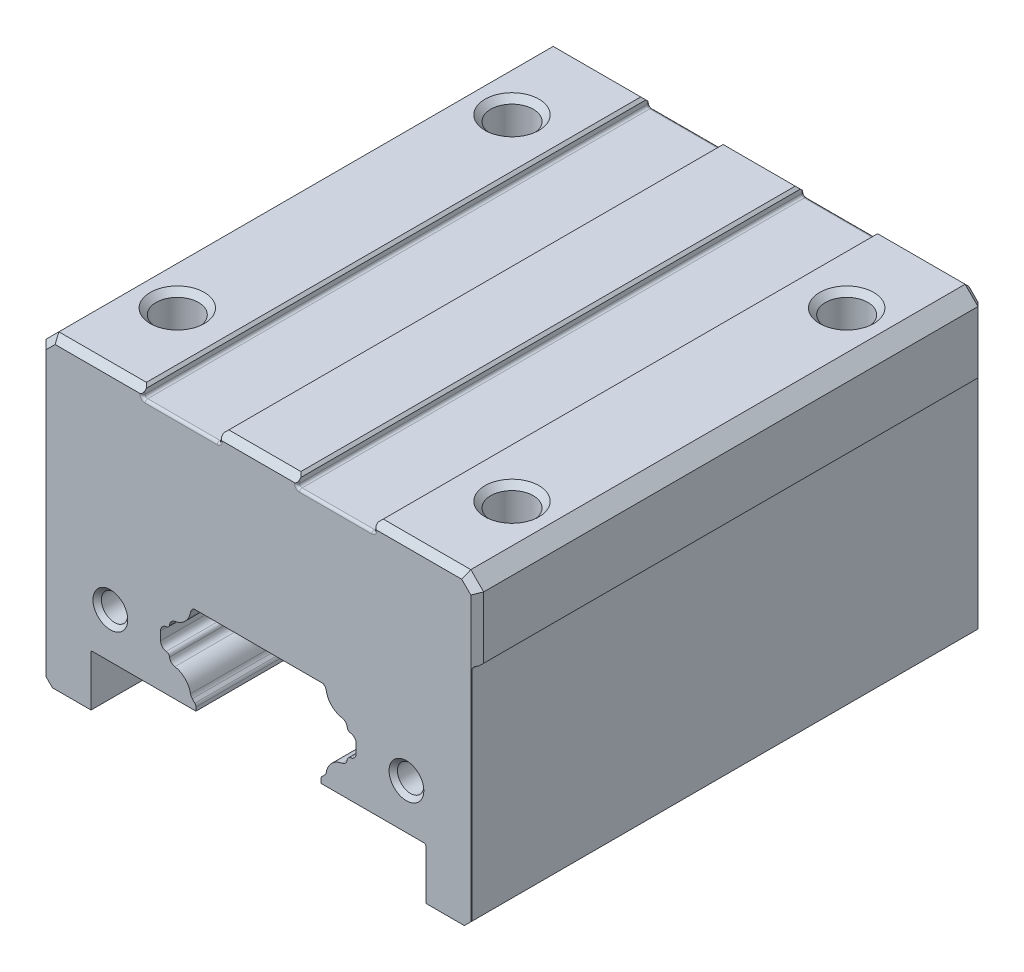
SolidWorks part; units mm, degrees
material "Plain Carbon Steel"
ref_plane "Front Plane" through (0, 0, 0) normal (0, 0, 1) x (1, 0, 0)
ref_plane "Top Plane" through (0, 0, 0) normal (0, 1, 0) x (1, 0, 0)
ref_plane "Right Plane" through (0, 0, 0) normal (1, 0, 0) x (0, 0, -1)
sketch "Rail Profile" plane through (0, 0, 0) normal (0, 0, 1) x (1, 0, 0)
  line L47 (0, 0) -> (0, 28) construction
  line L48 (-7, 0) -> (7, 0)
  line L49 (7, 0) -> (7.5, 0.5)
  line L50 (7.5, 0.5) -> (7.5, 3.0858)
  line L58 (7.2071, 3.7929) -> (4.8672, 6.1328)
  line L59 (4.75, 6.4157) -> (4.75, 8.5843)
  line L60 (4.8672, 8.8672) -> (5.063, 9.063)
  line L61 (7.5, 11.6657) -> (7.5, 12.3343)
  line L62 (-7, 0) -> (-7.5, 0.5)
  line L63 (5, 15) -> (-5, 15)
  line L64 (6.75, 9) -> (6.75, 15) construction
  line L65 (5.063, 14.937) -> (5, 15)
  line L66 (-7.5, 0.5) -> (-7.5, 3.0858)
  line L67 (6.75, 15) -> (3.75, 12) construction
  line L68 (3.75, 12) -> (6.75, 9) construction
  line L69 (7.1, 12.3343) -> (7.1, 11.6657) construction
  line L70 (6.4042, 13.0301) -> (6.4042, 10.9699) construction
  line L71 (-7.2071, 3.7929) -> (-4.8672, 6.1328)
  line L72 (-4.75, 6.4157) -> (-4.75, 8.5843)
  line L73 (-4.8672, 8.8672) -> (-5.063, 9.063)
  line L74 (5, 15) -> (8, 12) construction
  line L75 (4.8672, 8.8672) -> (8, 12) construction
  line L76 (-7.5, 11.6657) -> (-7.5, 12.3343)
  line L77 (-5.063, 14.937) -> (-5, 15)
  arc A4 (6.4734, 13.4241) -> (5.1741, 14.7234) centre (6.75, 15) cw
  arc A6 (5.1741, 9.2766) -> (6.4734, 10.5759) centre (6.75, 9) cw
  arc A7 (7.2071, 3.7929) -> (7.5, 3.0858) centre (6.5, 3.0858) cw
  arc A8 (5.063, 14.937) -> (5.1741, 14.7234) centre (4.7801, 14.6542) cw
  arc A9 (6.4734, 13.4241) -> (6.8012, 13.0792) centre (6.4042, 13.0301) cw
  arc A10 (7.1491, 12.7313) -> (7.5, 12.3343) centre (7.1, 12.3343) cw
  arc A11 (7.5, 11.6657) -> (7.1491, 11.2687) centre (7.1, 11.6657) cw
  arc A12 (6.8012, 10.9208) -> (6.4734, 10.5759) centre (6.4042, 10.9699) cw
  arc A13 (5.1741, 9.2766) -> (5.063, 9.063) centre (4.7801, 9.3458) cw
  arc A14 (4.8672, 8.8672) -> (4.75, 8.5843) centre (5.15, 8.5843) ccw
  arc A15 (4.75, 6.4157) -> (4.8672, 6.1328) centre (5.15, 6.4157) ccw
  arc A16 (6.8012, 13.0792) -> (7.1491, 12.7313) centre (7.1981, 13.1283) ccw
  arc A17 (7.1491, 11.2687) -> (6.8012, 10.9208) centre (7.1981, 10.8717) ccw
  arc A18 (-7.2071, 3.7929) -> (-7.5, 3.0858) centre (-6.5, 3.0858) ccw
  arc A19 (-4.75, 6.4157) -> (-4.8672, 6.1328) centre (-5.15, 6.4157) cw
  arc A20 (-4.8672, 8.8672) -> (-4.75, 8.5843) centre (-5.15, 8.5843) cw
  arc A21 (-5.1741, 9.2766) -> (-5.063, 9.063) centre (-4.7801, 9.3458) ccw
  arc A22 (-5.1741, 9.2766) -> (-6.4734, 10.5759) centre (-6.75, 9) ccw
  arc A23 (-6.8012, 10.9208) -> (-6.4734, 10.5759) centre (-6.4042, 10.9699) ccw
  arc A24 (-7.1491, 11.2687) -> (-6.8012, 10.9208) centre (-7.1981, 10.8717) cw
  arc A25 (-7.5, 11.6657) -> (-7.1491, 11.2687) centre (-7.1, 11.6657) ccw
  arc A26 (-7.1491, 12.7313) -> (-7.5, 12.3343) centre (-7.1, 12.3343) ccw
  arc A27 (-6.8012, 13.0792) -> (-7.1491, 12.7313) centre (-7.1981, 13.1283) cw
  arc A28 (-6.4734, 13.4241) -> (-6.8012, 13.0792) centre (-6.4042, 13.0301) ccw
  arc A29 (-6.4734, 13.4241) -> (-5.1741, 14.7234) centre (-6.75, 15) ccw
  arc A30 (-5.063, 14.937) -> (-5.1741, 14.7234) centre (-4.7801, 14.6542) ccw
  point P2 (4.75, 7.5)
  point P12 (7.5, 12)
  point P19 (6.75, 12)
  point P25 (5.1578, 14.8422)
  point P50 (8, 12)
  point P78 (0, 15)
  dimension "Rb" = 1.6
  dimension "Rf1" = 1
  dimension "Rf2" = 0.4
  dimension "WR" = 15
  dimension "Wi" = 9.5
  dimension "Wt" = 5
  dimension "Ac" = 135
  dimension "HR" = 15
  dimension "Hm" = 7.5
  dimension "Hb" = 12
  dimension "Hc" = 0.5
  dimension "Wb" = 7.5
sketch "Block Profile" plane through (0, 0, 0) normal (0, 0, 1) x (1, 0, 0)
  line L16 (16, 4.3) -> (13, 4.3)
  line L17 (0, 0) -> (0, 28) construction
  line L18 (17, 5.3) -> (17, 27)
  line L19 (16, 28) -> (-16, 28)
  line L20 (5.0414, 15.1) -> (-5.0414, 15.1)
  line L21 (0, 15.1) -> (0, 28) construction
  line L22 (17, 5.3) -> (16, 4.3)
  line L23 (17, 27) -> (16, 28)
  line L24 (13, 4.3) -> (13, 8.2)
  line L25 (12.9, 8.3) -> (4.85, 8.3)
  line L26 (-5.1337, 15.0077) -> (-5.0414, 15.1)
  line L27 (-7.6, 11.6657) -> (-7.6, 12.3343)
  line L28 (-4.9379, 8.7964) -> (-5.1337, 8.9923)
  line L29 (-4.85, 8.3) -> (-4.85, 8.5843)
  line L30 (-12.9, 8.3) -> (-4.85, 8.3)
  line L31 (-13, 4.3) -> (-13, 8.2)
  line L32 (5.0414, 15.1) -> (-5.0414, 15.1)
  line L33 (-5.0414, 15.1) -> (-5.1337, 15.0077)
  line L34 (-7.6, 12.3343) -> (-7.6, 11.6657)
  line L35 (-5.1337, 8.9923) -> (-4.9379, 8.7964)
  line L36 (-4.85, 8.5843) -> (-4.85, 6.4157)
  line L37 (-4.9379, 6.2036) -> (-7.2778, 3.8636)
  line L38 (-7.6, 3.0858) -> (-7.6, 0.4586)
  line L39 (-7.6, 0.4586) -> (-7.0414, -0.1)
  line L40 (-7.0414, -0.1) -> (7.0414, -0.1)
  line L41 (7.0414, -0.1) -> (7.6, 0.4586)
  line L42 (7.6, 0.4586) -> (7.6, 3.0858)
  line L43 (7.2778, 3.8636) -> (4.9379, 6.2036)
  line L44 (4.85, 6.4157) -> (4.85, 8.5843)
  line L45 (4.9379, 8.7964) -> (5.1337, 8.9923)
  line L46 (7.6, 11.6657) -> (7.6, 12.3343)
  line L47 (5.1337, 15.0077) -> (5.0414, 15.1)
  line L60 (4.85, 8.3) -> (4.85, 8.5843)
  line L61 (4.9379, 8.7964) -> (5.1337, 8.9923)
  line L62 (7.6, 11.6657) -> (7.6, 12.3343)
  line L63 (5.1337, 15.0077) -> (5.0414, 15.1)
  line L64 (-16, 4.3) -> (-13, 4.3)
  line L65 (-17, 5.3) -> (-16, 4.3)
  line L66 (-17, 5.3) -> (-17, 27)
  line L67 (-17, 27) -> (-16, 28)
  arc A26 (12.9, 8.3) -> (13, 8.2) centre (12.9, 8.2) cw
  arc A27 (-5.2726, 14.7406) -> (-5.1337, 15.0077) centre (-4.7801, 14.6542) cw
  arc A28 (-5.2726, 14.7406) -> (-6.4906, 13.5226) centre (-6.75, 15) cw
  arc A29 (-6.9004, 13.0915) -> (-6.4906, 13.5226) centre (-6.4042, 13.0301) cw
  arc A30 (-6.9004, 13.0915) -> (-7.1613, 12.8305) centre (-7.1981, 13.1283) cw
  arc A31 (-7.6, 12.3343) -> (-7.1613, 12.8305) centre (-7.1, 12.3343) cw
  arc A32 (-7.1613, 11.1695) -> (-7.6, 11.6657) centre (-7.1, 11.6657) cw
  arc A33 (-7.1613, 11.1695) -> (-6.9004, 10.9085) centre (-7.1981, 10.8717) cw
  arc A34 (-6.4906, 10.4774) -> (-6.9004, 10.9085) centre (-6.4042, 10.9699) cw
  arc A35 (-6.4906, 10.4774) -> (-5.2726, 9.2594) centre (-6.75, 9) cw
  arc A36 (-5.1337, 8.9923) -> (-5.2726, 9.2594) centre (-4.7801, 9.3458) cw
  arc A37 (-4.9379, 8.7964) -> (-4.85, 8.5843) centre (-5.15, 8.5843) cw
  arc A38 (-12.9, 8.3) -> (-13, 8.2) centre (-12.9, 8.2) ccw
  arc A52 (-5.1337, 15.0077) -> (-5.2726, 14.7406) centre (-4.7801, 14.6542) ccw
  arc A53 (-6.4906, 13.5226) -> (-5.2726, 14.7406) centre (-6.75, 15) ccw
  arc A54 (-6.4906, 13.5226) -> (-6.9004, 13.0915) centre (-6.4042, 13.0301) ccw
  arc A55 (-7.1613, 12.8305) -> (-6.9004, 13.0915) centre (-7.1981, 13.1283) ccw
  arc A56 (-7.1613, 12.8305) -> (-7.6, 12.3343) centre (-7.1, 12.3343) ccw
  arc A57 (-7.6, 11.6657) -> (-7.1613, 11.1695) centre (-7.1, 11.6657) ccw
  arc A58 (-6.9004, 10.9085) -> (-7.1613, 11.1695) centre (-7.1981, 10.8717) ccw
  arc A59 (-6.9004, 10.9085) -> (-6.4906, 10.4774) centre (-6.4042, 10.9699) ccw
  arc A60 (-5.2726, 9.2594) -> (-6.4906, 10.4774) centre (-6.75, 9) ccw
  arc A61 (-5.2726, 9.2594) -> (-5.1337, 8.9923) centre (-4.7801, 9.3458) ccw
  arc A62 (-4.85, 8.5843) -> (-4.9379, 8.7964) centre (-5.15, 8.5843) ccw
  arc A63 (-4.9379, 6.2036) -> (-4.85, 6.4157) centre (-5.15, 6.4157) ccw
  arc A64 (-7.2778, 3.8636) -> (-7.6, 3.0858) centre (-6.5, 3.0858) ccw
  arc A65 (7.6, 3.0858) -> (7.2778, 3.8636) centre (6.5, 3.0858) ccw
  arc A66 (4.85, 6.4157) -> (4.9379, 6.2036) centre (5.15, 6.4157) ccw
  arc A67 (4.9379, 8.7964) -> (4.85, 8.5843) centre (5.15, 8.5843) ccw
  arc A68 (5.1337, 8.9923) -> (5.2726, 9.2594) centre (4.7801, 9.3458) ccw
  arc A69 (6.4906, 10.4774) -> (5.2726, 9.2594) centre (6.75, 9) ccw
  arc A70 (6.4906, 10.4774) -> (6.9004, 10.9085) centre (6.4042, 10.9699) ccw
  arc A71 (7.1613, 11.1695) -> (6.9004, 10.9085) centre (7.1981, 10.8717) ccw
  arc A72 (7.1613, 11.1695) -> (7.6, 11.6657) centre (7.1, 11.6657) ccw
  arc A73 (7.6, 12.3343) -> (7.1613, 12.8305) centre (7.1, 12.3343) ccw
  arc A74 (6.9004, 13.0915) -> (7.1613, 12.8305) centre (7.1981, 13.1283) ccw
  arc A75 (6.9004, 13.0915) -> (6.4906, 13.5226) centre (6.4042, 13.0301) ccw
  arc A76 (5.2726, 14.7406) -> (6.4906, 13.5226) centre (6.75, 15) ccw
  arc A77 (5.2726, 14.7406) -> (5.1337, 15.0077) centre (4.7801, 14.6542) ccw
  arc A93 (4.9379, 8.7964) -> (4.85, 8.5843) centre (5.15, 8.5843) ccw
  arc A94 (5.1337, 8.9923) -> (5.2726, 9.2594) centre (4.7801, 9.3458) ccw
  arc A95 (6.4906, 10.4774) -> (5.2726, 9.2594) centre (6.75, 9) ccw
  arc A96 (6.4906, 10.4774) -> (6.9004, 10.9085) centre (6.4042, 10.9699) ccw
  arc A97 (7.1613, 11.1695) -> (6.9004, 10.9085) centre (7.1981, 10.8717) ccw
  arc A98 (7.1613, 11.1695) -> (7.6, 11.6657) centre (7.1, 11.6657) ccw
  arc A99 (7.6, 12.3343) -> (7.1613, 12.8305) centre (7.1, 12.3343) ccw
  arc A100 (6.9004, 13.0915) -> (7.1613, 12.8305) centre (7.1981, 13.1283) ccw
  arc A101 (6.9004, 13.0915) -> (6.4906, 13.5226) centre (6.4042, 13.0301) ccw
  arc A102 (5.2726, 14.7406) -> (6.4906, 13.5226) centre (6.75, 15) ccw
  arc A103 (5.2726, 14.7406) -> (5.1337, 15.0077) centre (4.7801, 14.6542) ccw
  point P0 (17, 4.3)
  point P5 (17, 28)
  point P15 (13, 8.3)
  dimension "D9" = 0.1
  dimension "D2" = 4.3
  dimension "D3" = 17
  dimension "D4" = 23.7
  dimension "D5" = 4
  dimension "D6" = 13
  dimension "D1" = 0.1
extrude "Block Body" add sketch "Block Profile" along normal mid plane 39.4
sketch "Side Reference Sketch" plane through (17, 0, 0) normal (1, 0, 0) x (0, 0, -1)
  line L0 (0, 0) -> (0, 28) construction
  line L1 (-20, 22) -> (20, 22)
  line L2 (-20, 22) -> (-20, 2)
  line L3 (-20, 2) -> (20, 2)
  line L4 (20, 22) -> (20, 2)
  line L5 (-20, 22) -> (20, 2) construction
  line L6 (-20, 2) -> (20, 22) construction
  line L7 (-19.7, 28) -> (19.7, 28) construction
  point P0 (0, 12)
  dimension "D1" = 20
  dimension "D2" = 40
  dimension "D3" = 6
extrude "Side Reference" cut sketch "Side Reference Sketch" against normal blind 0.45
chamfer "Aesthetic Chamfer 1" distance 0.5 angle 45 10 edges at (-17, 16.15, -19.7) (-16.5, 27.5, -19.7) (0, 28, -19.7) (16.5, 27.5, -19.7) (17, 24.5, -19.7) (-17, 16.15, 19.7) (-16.5, 27.5, 19.7) (17, 24.5, 19.7) (16.5, 27.5, 19.7) (0, 28, 19.7)
sketch "Casting Groove Sketch" plane through (0, 28, 0) normal (0, 1, 0) x (1, 0, 0)
  line L0 (-6, 0) -> (6, 0) construction
  line L1 (-9, 20) -> (-3, 20)
  line L2 (-9, 20) -> (-9, -20)
  line L3 (-9, -20) -> (-3, -20)
  line L4 (-3, 20) -> (-3, -20)
  line L5 (-9, 20) -> (-3, -20) construction
  line L6 (-9, -20) -> (-3, 20) construction
  line L7 (3, 20) -> (9, 20)
  line L8 (3, 20) -> (3, -20)
  line L9 (3, -20) -> (9, -20)
  line L10 (9, 20) -> (9, -20)
  line L11 (3, 20) -> (9, -20) construction
  line L12 (3, -20) -> (9, 20) construction
  point P0 (-6, 0)
  point P5 (6, 0)
  point P12 (0, 0)
  dimension "D1" = 40
  dimension "D2" = 6
  dimension "D3" = 40
  dimension "D4" = 6
  dimension "D5" = 12
extrude "Casting Goorve" cut sketch "Casting Groove Sketch" against normal blind 0.75
chamfer "Aesthetic Chamfer 2" distance 0.2 angle 45 5 edges at (-9, 28, 0) (-3, 28, 0) (3, 28, 0) (9, 28, 0) (17, 22, 0)
fillet "Production Fillet" radius 0.2 17 edges at (3, 27.375, -19.7) (3, 27.375, 19.7) (9, 27.375, -19.7) (9, 27.375, 19.7) (-9, 27.375, -19.7) (-9, 27.375, 19.7) (-3, 27.375, -19.7) (-3, 27.375, 19.7) (3, 27.25, 0) (6, 27.25, -19.7) (9, 27.25, 0) (6, 27.25, 19.7) (-9, 27.25, 0) (-6, 27.25, -19.7) (-3, 27.25, 0) (-6, 27.25, 19.7) (16.55, 22, 0)
hole_wizard "Fixing Holes" positions "Sketch4" profile "Sketch5" tap size "M4" standard "ISO"
sketch "Sketch4" plane through (0, 28, 0) normal (0, 1, 0) x (1, 0, 0)
  line L1 (-13, -13) -> (13, -13) construction
  line L2 (-13, -13) -> (-13, 13) construction
  line L3 (-13, 13) -> (13, 13) construction
  line L4 (13, -13) -> (13, 13) construction
  line L5 (-13, -13) -> (13, 13) construction
  line L6 (-13, 13) -> (13, -13) construction
  line L7 (17, -19.2) -> (17, 19.2) construction
  line L9 (-9.2, -19.7) -> (-15.7929, -19.7) construction
  point P0 (-13, -13)
  point P2 (-13, 13)
  point P4 (13, 13)
  point P6 (13, -13)
  point P32 (0, 0)
  dimension "D1" = 26
  dimension "D2" = 4
  dimension "D3" = 19.7
sketch "Sketch5" plane through (-13, 28, 13) normal (1, 0, 0) x (0, 0, 1)
  line L0 (0, 0) -> (0, 8.0914)
  line L1 (0, 8.0914) -> (1.65, 7.1)
  line L2 (1.65, 7.1) -> (1.65, 0.45)
  line L3 (1.65, 0.45) -> (2.1, 0)
  line L5 (2.1, 0) -> (0, 0)
  line L6 (-1.65, 0.45) -> (-2.1, 0) construction
  line L10 (0, 8.0914) -> (-1.65, 7.1) construction
  line L11 (0, -6.35) -> (0, 107.95) construction
  dimension "Tap Drill Dia." = 3.3
  dimension "Tap Drill Depth" = 7.1
  dimension "Near C'Sink Dia." = 4.2
  dimension "Near C'Sink Angle" = 90
  dimension "Drill Angle" = 118
cosmetic thread "Hole Thread1" parameters "D1"=5, "D2"=4
cosmetic thread "Hole Thread2" parameters "D1"=5, "D2"=4
cosmetic thread "Hole Thread3" parameters "D1"=5, "D2"=4
cosmetic thread "Hole Thread4" parameters "D1"=5, "D2"=4
hole_wizard "End Cap Fixing Holes Front" positions "Sketch6" profile "Sketch7" tap size "M2.5" standard "ISO"
sketch "Sketch6" plane through (0, 0, 19.7) normal (0, 0, 1) x (1, 0, 0)
  line L0 (11.5, 11.8) -> (-11.5, 11.8) construction
  line L2 (0, 0) -> (0, 28) construction
  line L5 (13, 4.3) -> (16, 4.3) construction
  point P0 (-11.5, 11.8)
  point P2 (11.5, 11.8)
  point P9 (0, 11.8)
  dimension "D1" = 23
  dimension "D2" = 7.5
sketch "Sketch7" plane through (-11.5, 11.8, 19.7) normal (1, 0, 0) x (0, -1, 0)
  line L0 (0, 0) -> (0, 6.9659)
  line L1 (0, 6.9659) -> (1.025, 6.35)
  line L2 (1.025, 6.35) -> (1.025, 0.325)
  line L3 (1.025, 0.325) -> (1.35, 0)
  line L5 (1.35, 0) -> (0, 0)
  line L6 (-1.025, 0.325) -> (-1.35, 0) construction
  line L10 (0, 6.9659) -> (-1.025, 6.35) construction
  line L11 (0, -6.35) -> (0, 107.95) construction
  dimension "Tap Drill Dia." = 2.05
  dimension "Tap Drill Depth" = 6.35
  dimension "Near C'Sink Dia." = 2.7
  dimension "Near C'Sink Angle" = 90
  dimension "Drill Angle" = 118
cosmetic thread "Hole Thread5" parameters "D1"=5, "D2"=2.5
cosmetic thread "Hole Thread6" parameters "D1"=5, "D2"=2.5
hole_wizard "End Cap Fixing Holes Back" positions "Sketch9" profile "Sketch10" tap size "M2.5" standard "ISO"
sketch "Sketch9" plane through (0, 0, -19.7) normal (0, 0, -1) x (-1, 0, 0)
  line L0 (-11.5, 11.8) -> (11.5, 11.8) construction
  line L2 (2.8, 27.5) -> (-2.8, 27.5) construction
  line L4 (-13, 4.3) -> (-16, 4.3) construction
  point P0 (-11.5, 11.8)
  point P2 (11.5, 11.8)
  point P9 (0, 11.8)
  point P12 (0, 27.5)
  dimension "D1" = 23
  dimension "D2" = 7.5
sketch "Sketch10" plane through (11.5, 11.8, -19.7) normal (1, 0, 0) x (0, 1, 0)
  line L0 (0, 0) -> (0, 6.9659)
  line L1 (0, 6.9659) -> (1.025, 6.35)
  line L2 (1.025, 6.35) -> (1.025, 0.325)
  line L3 (1.025, 0.325) -> (1.35, 0)
  line L5 (1.35, 0) -> (0, 0)
  line L6 (-1.025, 0.325) -> (-1.35, 0) construction
  line L10 (0, 6.9659) -> (-1.025, 6.35) construction
  line L11 (0, -6.35) -> (0, 107.95) construction
  dimension "Tap Drill Dia." = 2.05
  dimension "Tap Drill Depth" = 6.35
  dimension "Near C'Sink Dia." = 2.7
  dimension "Near C'Sink Angle" = 90
  dimension "Drill Angle" = 118
cosmetic thread "Hole Thread8" parameters "D1"=5, "D2"=2.5
cosmetic thread "Hole Thread9" parameters "D1"=5, "D2"=2.5
equation "\"Wt@Rail Profile\"= \"WR@Rail Profile\" / 3'Top Side Half Width"
equation "\"Hm@Rail Profile\"= \"HR@Rail Profile\" / 2'Recirculation Avoidance Height"
equation "\"Hb@Rail Profile\"= 0.8 * \"HR@Rail Profile\"'Pivot Height"
equation "\"Hc@Rail Profile\"= \"WR@Rail Profile\" / 30'Chamfer Width"
equation "\"Wb@Rail Profile\"= \"WR@Rail Profile\" / 2'Ball Center Cross Width"
